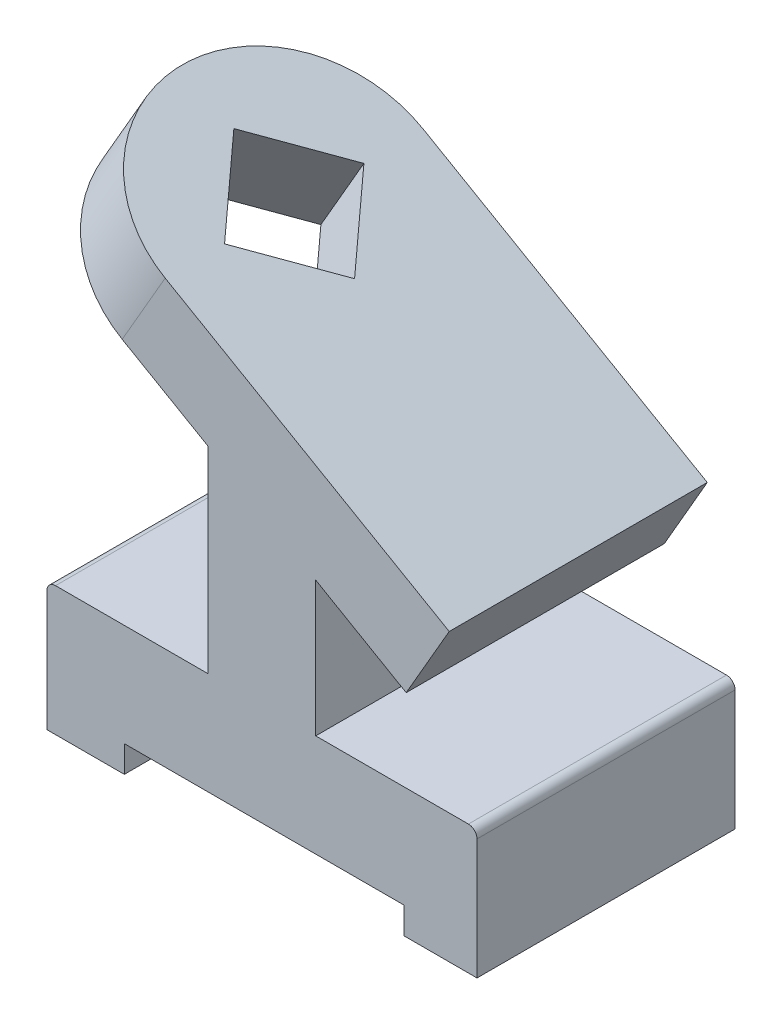
SolidWorks part; units mm, degrees
ref_plane "Front Plane" through (0, 0, 0) normal (0, 0, 1) x (1, 0, 0)
ref_plane "Top Plane" through (0, 0, 0) normal (0, 1, 0) x (1, 0, 0)
ref_plane "Right Plane" through (0, 0, 0) normal (1, 0, 0) x (0, 0, -1)
sketch "Sketch1" plane through (0, 0, 0) normal (0, 0, 1) x (1, 0, 0)
  line L0 (-78.0575, 0) -> (-30.4325, 0)
  line L1 (-78.0575, 0) -> (-78.0575, -38.1)
  line L2 (-78.0575, -38.1) -> (-55.1975, -38.1)
  line L3 (-55.1975, -38.1) -> (-55.1975, -30.2363)
  line L4 (-55.1975, -30.2363) -> (27.3525, -30.2363)
  line L5 (27.3525, -30.2363) -> (27.3525, -38.1)
  line L6 (27.3525, -38.1) -> (48.9425, -38.1)
  line L7 (48.9425, 0) -> (48.9425, -38.1)
  line L8 (-30.4325, 0) -> (-30.4325, 58.166)
  line L9 (-30.4325, 58.166) -> (1.3175, 58.166)
  line L10 (1.3175, 58.166) -> (1.3175, 0)
  line L11 (1.3175, 0) -> (48.9425, 0)
  point P4 (0, 0)
  point P11 (27.3525, -34.1682)
  dimension "D1" = 82.55
  dimension "D2" = 105.41
  dimension "D3" = 38.1
  dimension "D4" = 127
  dimension "D5" = 58.166
extrude "Boss-Extrude1" add sketch "Sketch1" along normal blind 38.1 and the other way blind 38.1
ref_plane "Plane1" through (-55.1975, -38.1, 38.1) normal (0, 1, 0) x (1, 0, 0)
fillet "Fillet3" radius 2.54 1 edges at (48.9425, 0, 0)
fillet "Fillet4" radius 2.54 1 edges at (-78.0575, 0, 0)
sketch "Sketch5" plane through (0, 0, 38.1) normal (0, 0, 1) x (1, 0, 0)
  line L0 (-55.8325, 72.8307) -> (28.0312, 24.4119)
  line L1 (-55.8325, 72.8307) -> (-43.1325, 94.8277)
  line L3 (-43.1325, 94.8277) -> (40.7312, 46.409)
  line L4 (40.7312, 46.409) -> (28.0312, 24.4119)
  dimension "D1" = 96.8375
  dimension "D2" = 29.3294
extrude "Boss-Extrude2" add sketch "Sketch5" against normal blind 76.2
sketch "Sketch6" plane through (30.2785, 52.4439, 0) normal (0.5, 0.866, 0) x (0.866, -0.5, 0)
  line L0 (-84.7677, 38.1) -> (-84.7677, -38.1) construction
  circle A0 centre (-84.7677, 0) radius 38.1
extrude "Boss-Extrude3" add sketch "Sketch6" against normal blind 25.4
sketch "Sketch7" plane through (17.5785, 30.4468, 0) normal (-0.5, -0.866, 0) x (-0.866, 0.5, 0)
  line L0 (84.7677, 20.574) -> (105.3417, 0)
  line L3 (105.3417, 0) -> (84.7677, -20.574)
  line L4 (84.7677, -20.574) -> (64.1937, 0)
  line L5 (64.1937, 0) -> (84.7677, 20.574)
  line L6 (55.4383, 38.1) -> (55.4383, -38.1) construction
  point P4 (84.7677, 0)
  point P5 (0, 0)
  point P8 (84.7677, 0)
  dimension "D1" = 29.096
  dimension "D2" = 8.7554
  dimension "D3" = 17.526
extrude "Cut-Extrude2" cut sketch "Sketch7" against normal through all contours L3 L4 L5 L0
